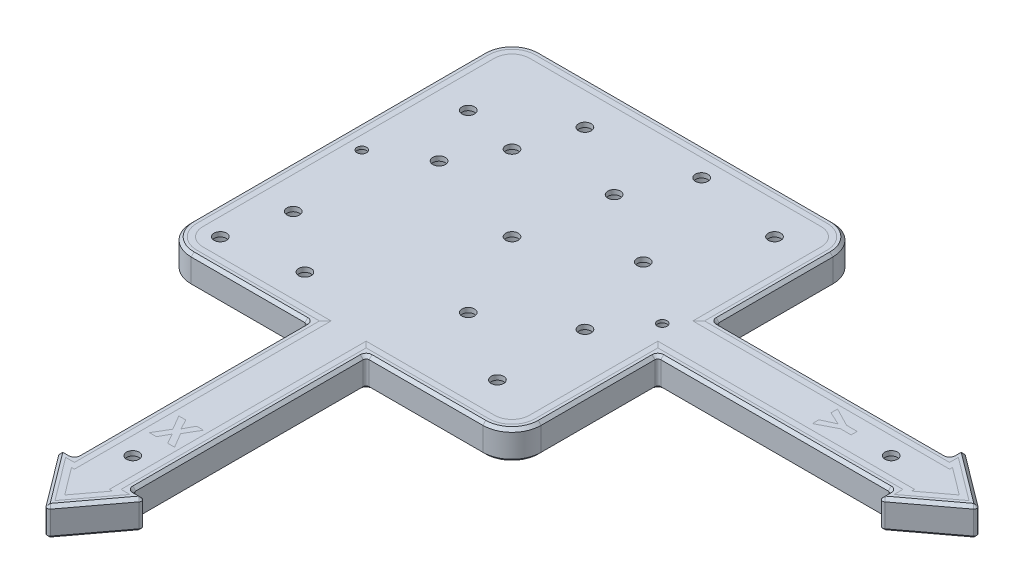
SolidWorks part; units mm, degrees
note: The reader was unsure of these and kept them because the rebuilt part matched: shared geometry of "Sketch7<3>", "Sketch7<4>", "Sketch7<5>", "Sketch7<6>", "Sketch7<7>", "Sketch8<2>", "Sketch9<2>".
ref_plane "Front Plane" through (0, 0, 0) normal (0, 0, 1) x (1, 0, 0)
ref_plane "Top Plane" through (0, 0, 0) normal (0, 1, 0) x (1, 0, 0)
ref_plane "Right Plane" through (0, 0, 0) normal (1, 0, 0) x (0, 0, -1)
sketch "Sketch1" plane through (0, 0, 0) normal (0, 1, 0) x (1, 0, 0)
  line L0 (-10, -60) -> (-10, -140)
  line L1 (-60, -60) -> (-10, -60)
  line L2 (-60, -60) -> (-60, 60)
  line L3 (-60, 60) -> (60, 60)
  line L4 (60, -60) -> (60, -10)
  line L5 (-60, -60) -> (60, 60) construction
  line L6 (-60, 60) -> (60, -60) construction
  line L7 (-10, -140) -> (10, -140)
  line L8 (10, -140) -> (10, -60)
  line L9 (60, -10) -> (140, -10)
  line L10 (140, -10) -> (140, 10)
  line L11 (140, 10) -> (60, 10)
  line L12 (0, 0) -> (140, 0) construction
  line L13 (0, 0) -> (0, -140) construction
  line L14 (10, -60) -> (60, -60)
  line L15 (60, 10) -> (60, 60)
  point P0 (0, 0)
  point P12 (140, 0)
  point P16 (0, -140)
  dimension "D1" = 120
  dimension "D2" = 20
  dimension "D3" = 80
  dimension "D4" = 120
extrude "Boss-Extrude1" add sketch "Sketch1" along normal blind 10
sketch "Sketch2" plane through (0, 10, 0) normal (0, 1, 0) x (1, 0, 0)
  line L0 (0, 0) -> (140, 0) construction
  line L1 (140, -10) -> (140, 10) construction
  line L2 (0, 0) -> (0, -140) construction
  line L3 (-10, -140) -> (10, -140) construction
  line L4 (-60, 60) -> (-60, -60) construction
  circle A0 centre (0, 0) radius 2.15
  circle A1 centre (130, 0) radius 2.15
  circle A2 centre (0, -130) radius 2.15
  circle A3 centre (40, -45) radius 2.15
  circle A4 centre (-45, -30) radius 2.15
  circle A5 centre (-26, 26) radius 2.15
  circle A6 centre (45, 45) radius 2.15
  circle A7 centre (15, 50) radius 2.15
  circle A8 centre (40, -15) radius 2.15
  circle A9 centre (-25, -46) radius 2.15
  circle A10 centre (-45, 30) radius 2.15
  circle A11 centre (-20, 45) radius 2.15
  circle A12 centre (15, -30) radius 2.15
  circle A13 centre (30, 15) radius 2.15
  circle A15 centre (-35, 10) radius 2.15
  circle A16 centre (5, 30) radius 2.15
  circle A17 centre (-50, -50) radius 2.15
  dimension "D1" = 4.3
  dimension "D12" = 50
  dimension "D21" = 40
  dimension "D22" = 35
  dimension "D23" = 15
  dimension "D24" = 30
  dimension "D25" = 15
  dimension "D26" = 30
  dimension "D27" = 10
  dimension "D28" = 50
  dimension "D29" = 50
  dimension "D30" = 30
  dimension "D31" = 5
  dimension "D2" = 130
  dimension "D3" = 130
  dimension "D4" = 40
  dimension "D5" = 45
  dimension "D6" = 45
  dimension "D7" = 30
  dimension "D8" = 26
  dimension "D9" = 26
  dimension "D10" = 45
  dimension "D11" = 45
  dimension "D13" = 15
  dimension "D14" = 30
  dimension "D15" = 45
  dimension "D16" = 46
  dimension "D17" = 25
  dimension "D18" = 40
  dimension "D19" = 15
  dimension "D20" = 45
extrude "Cut-Extrude1" cut sketch "Sketch2" against normal through all
sketch "Sketch3" plane through (0, 10, 0) normal (0, 1, 0) x (1, 0, 0)
  line L0 (-51.5, 0) -> (51.5, 0) construction
  circle A0 centre (51.5, 0) radius 1.65
  circle A1 centre (-51.5, 0) radius 1.65
  point P5 (0, 0)
  point P9 (0, 0)
  dimension "D2" = 3.3
  dimension "D1" = 103
extrude "Cut-Extrude2" cut sketch "Sketch3" against normal through all
sketch "Sketch4" plane through (0, 0, 0) normal (0, -1, 0) x (1, 0, 0)
  circle A0 centre (-45, 30) radius 5
  circle A1 centre (40, 45) radius 5
  circle A2 centre (0, 130) radius 5
  circle A3 centre (130, 0) radius 5
  circle A4 centre (0, 0) radius 5
  circle A5 centre (-26, -26) radius 5
  circle A6 centre (45, -45) radius 5
  circle A7 centre (40, 15) radius 5
  circle A8 centre (-25, 46) radius 5
  circle A9 centre (-45, -30) radius 5
  circle A10 centre (15, -50) radius 5
  circle A11 centre (15, 30) radius 5
  circle A12 centre (30, -15) radius 5
  circle A13 centre (-20, -45) radius 5
  circle A14 centre (-35, -10) radius 5
  circle A15 centre (5, -30) radius 5
  circle A16 centre (-50, 50) radius 5
  dimension "D1" = 10
extrude "Cut-Extrude3" cut sketch "Sketch4" against normal offset from surface (8.4 mm away) 1.6 up to face at (51.5, 10, 1.65)
sketch "Sketch5" plane through (0, 0, 0) normal (0, -1, 0) x (1, 0, 0)
  circle A0 centre (-51.5, 0) radius 3
  circle A1 centre (51.5, 0) radius 3
  dimension "D1" = 6
extrude "Cut-Extrude4" cut sketch "Sketch5" against normal offset from surface (9 mm away) 1 up to face at (51.5, 10, 1.65)
fillet "Fillet1" radius 10 4 edges at (-60, 5, -60) (60, 5, -60) (-60, 5, 60) (60, 5, 60)
sketch "Sketch6" plane through (0, 10, 0) normal (0, 1, 0) x (1, 0, 0)
  line L0 (0, -140) -> (0, -160) construction
  line L1 (-10, -140) -> (10, -140) construction
  line L2 (140, 0) -> (160, 0) construction
  line L3 (140, -10) -> (140, 10) construction
  line L4 (0, -140) -> (15, -140)
  line L5 (15, -140) -> (0, -160)
  line L6 (0, -160) -> (-15, -140)
  line L7 (-15, -140) -> (0, -140)
  line L8 (140, 0) -> (140, -15)
  line L9 (140, -15) -> (160, 0)
  line L10 (160, 0) -> (140, 15)
  line L11 (140, 15) -> (140, 0)
  dimension "D1" = 15
  dimension "D2" = 20
extrude "Boss-Extrude2" add sketch "Sketch6" against normal up to surface (10 mm away) up to face at (-51.5, 0, -3)
sketch "Sketch7" plane through (0, 10, 0) normal (0, 1, 0) x (1, 0, 0)
  line L36 (50, 58) -> (-50, 58)
  line L37 (-58, 50) -> (-58, -50)
  line L38 (-50, -58) -> (-8, -58)
  line L39 (-8, -58) -> (-8, -142)
  line L40 (-8, -142) -> (-11, -142)
  line L41 (-11, -142) -> (0, -156.6667)
  line L42 (0, -156.6667) -> (11, -142)
  line L43 (11, -142) -> (8, -142)
  line L44 (8, -142) -> (8, -58)
  line L45 (8, -58) -> (50, -58)
  line L46 (58, -50) -> (58, -8)
  line L47 (58, -8) -> (142, -8)
  line L48 (142, -8) -> (142, -11)
  line L49 (142, -11) -> (156.6667, 0)
  line L50 (156.6667, 0) -> (142, 11)
  line L51 (142, 11) -> (142, 8)
  line L52 (142, 8) -> (58, 8)
  line L53 (58, 8) -> (58, 50)
  line L54 (50, 58) -> (-50, 58)
  line L55 (-58, 50) -> (-58, -50)
  line L56 (-50, -58) -> (-8, -58)
  line L57 (-8, -58) -> (-8, -142)
  line L58 (-8, -142) -> (-11, -142)
  line L59 (-11, -142) -> (0, -156.6667)
  line L60 (0, -156.6667) -> (11, -142)
  line L61 (11, -142) -> (8, -142)
  line L62 (8, -142) -> (8, -58)
  line L63 (8, -58) -> (50, -58)
  line L64 (58, -50) -> (58, -8)
  line L65 (58, -8) -> (142, -8)
  line L66 (142, -8) -> (142, -11)
  line L67 (142, -11) -> (156.6667, 0)
  line L68 (156.6667, 0) -> (142, 11)
  line L69 (142, 11) -> (142, 8)
  line L70 (142, 8) -> (58, 8)
  line L71 (58, 8) -> (58, 50)
  line L72 (-6, -56) -> (-8, -58)
  line L73 (8, -58) -> (6, -56)
  line L74 (56, -6) -> (58, -8)
  line L75 (58, 8) -> (56, 6)
  line L90 (50, 56) -> (-50, 56)
  line L91 (-56, 50) -> (-56, -50)
  line L92 (-50, -56) -> (-6, -56)
  line L93 (-6, -56) -> (-6, -144)
  line L94 (-6, -144) -> (-7, -144)
  line L95 (-7, -144) -> (0, -153.3333)
  line L96 (0, -153.3333) -> (7, -144)
  line L97 (7, -144) -> (6, -144)
  line L98 (6, -144) -> (6, -56)
  line L99 (6, -56) -> (50, -56)
  line L100 (56, -50) -> (56, -6)
  line L101 (56, -6) -> (144, -6)
  line L102 (144, -6) -> (144, -7)
  line L103 (144, -7) -> (153.3333, 0)
  line L104 (153.3333, 0) -> (144, 7)
  line L105 (144, 7) -> (144, 6)
  line L106 (144, 6) -> (56, 6)
  line L107 (56, 6) -> (56, 50)
  line L108 (50, 56) -> (-50, 56)
  line L109 (-56, 50) -> (-56, -50)
  line L110 (-50, -56) -> (-6, -56)
  line L111 (-6, -56) -> (-6, -144)
  line L112 (-6, -144) -> (-7, -144)
  line L113 (-7, -144) -> (0, -153.3333)
  line L114 (0, -153.3333) -> (7, -144)
  line L115 (7, -144) -> (6, -144)
  line L116 (6, -144) -> (6, -56)
  line L117 (6, -56) -> (50, -56)
  line L118 (56, -50) -> (56, -6)
  line L119 (56, -6) -> (144, -6)
  line L120 (144, -6) -> (144, -7)
  line L121 (144, -7) -> (153.3333, 0)
  line L122 (153.3333, 0) -> (144, 7)
  line L123 (144, 7) -> (144, 6)
  line L124 (144, 6) -> (56, 6)
  line L125 (56, 6) -> (56, 50)
  arc A8 (-50, 58) -> (-58, 50) centre (-50, 50) ccw
  arc A9 (-58, -50) -> (-50, -58) centre (-50, -50) ccw
  arc A10 (50, -58) -> (58, -50) centre (50, -50) ccw
  arc A11 (58, 50) -> (50, 58) centre (50, 50) ccw
  arc A12 (-50, 58) -> (-58, 50) centre (-50, 50) ccw
  arc A13 (-58, -50) -> (-50, -58) centre (-50, -50) ccw
  arc A14 (50, -58) -> (58, -50) centre (50, -50) ccw
  arc A15 (58, 50) -> (50, 58) centre (50, 50) ccw
  arc A20 (-50, 56) -> (-56, 50) centre (-50, 50) ccw
  arc A21 (-56, -50) -> (-50, -56) centre (-50, -50) ccw
  arc A22 (50, -56) -> (56, -50) centre (50, -50) ccw
  arc A23 (56, 50) -> (50, 56) centre (50, 50) ccw
  arc A24 (-50, 56) -> (-56, 50) centre (-50, 50) ccw
  arc A25 (-56, -50) -> (-50, -56) centre (-50, -50) ccw
  arc A26 (50, -56) -> (56, -50) centre (50, -50) ccw
  arc A27 (56, 50) -> (50, 56) centre (50, 50) ccw
  dimension "D1" = 2
  dimension "D2" = 4
extrude "Cut-Extrude5" cut sketch "Sketch7" against normal blind 1 contours L116 L115 L114 L113 L112 L111 L72 L57 L58 L59 L60 L61 L62 L73
extrude "Boss-Extrude3" add sketch "Sketch7<3>" against normal up to surface (1 mm away) separate body contours L116 L115 L114 L113 L112 L111 L72 L57 L58 L59 L60 L61 L62 L73 up to face at (0, 9, 120.1429)
sketch "Sketch7<3>" plane through (0, 10, 0) normal (0, 1, 0) x (1, 0, 0) same geometry as "Sketch7"
extrude "Cut-Extrude6" cut sketch "Sketch7<4>" against normal blind 1 contours L124 L123 L122 L121 L120 L119 L74 L65 L66 L67 L68 L69 L70 L75
sketch "Sketch7<4>" plane through (0, 10, 0) normal (0, 1, 0) x (1, 0, 0) same geometry as "Sketch7"
extrude "Boss-Extrude4" add sketch "Sketch7<5>" against normal up to surface (1 mm away) separate body contours L124 L123 L122 L121 L120 L119 L74 L65 L66 L67 L68 L69 L70 L75 up to face at (120.1429, 9, 0)
sketch "Sketch7<5>" plane through (0, 10, 0) normal (0, 1, 0) x (1, 0, 0) same geometry as "Sketch7"
extrude "Cut-Extrude7" cut sketch "Sketch7<6>" against normal blind 1 contours A27 L125 L75 L71 A15 L54 A12 L55 A13 L56 L72 L110 A25 L109 A24 L108 | A26 L117 L73 L63 A14 L64 L74 L118
sketch "Sketch7<6>" plane through (0, 10, 0) normal (0, 1, 0) x (1, 0, 0) same geometry as "Sketch7"
extrude "Boss-Extrude5" add sketch "Sketch7<7>" against normal up to surface (1 mm away) separate body contours A27 L125 L75 L71 A15 L54 A12 L55 A13 L56 L72 L110 A25 L109 A24 L108 | A26 L117 L73 L63 A14 L64 L74 L118 up to face at (38.2424, 9, 38.2424)
sketch "Sketch7<7>" plane through (0, 10, 0) normal (0, 1, 0) x (1, 0, 0) same geometry as "Sketch7"
fillet "Fillet2" radius 1 14 edges at (60, 5, -10) (-10, 5, 60) (10, 5, 60) (60, 5, 10) (140, 5, 15) (140, 5, 10) (140, 5, -15) (140, 5, -10) (160, 5, 0) (-10, 5, 140) (-15, 5, 140) (0, 5, 160) (10, 5, 140) (15, 5, 140)
chamfer "Chamfer1" distance 1 angle 45 72 edges at (10, 0, 100) (10, 10, 100) (10.2929, 10, 60.2929) (10.2929, 0, 60.2929) (10.2929, 10, 139.7071) (10.2929, 0, 139.7071) (30.5, 10, 60) (30.5, 0, 60) (12, 0, 140) (57.0711, 10, 57.0711) (57.0711, 0, 57.0711) (13.8944, 0, 140.5528) (13.8944, 10, 140.5528) (60, 0, 30.5) (60, 10, 30.5) (7.3, 0, 150.2667) (60.2929, 10, 10.2929) (60.2929, 0, 10.2929) (0, 0, 159.3333) (0, 10, 159.3333) (100, 10, 10) (100, 0, 10) (-7.3, 0, 150.2667) (139.7071, 10, 10.2929) (139.7071, 0, 10.2929) (-13.8944, 0, 140.5528) (-13.8944, 10, 140.5528) (140, 0, 12) (-12, 0, 140) (140.5528, 0, 13.8944) (140.5528, 10, 13.8944) (-10.2929, 10, 139.7071) (-10.2929, 0, 139.7071) (150.2667, 0, 7.3) (-10, 10, 100) (-10, 0, 100) (159.3333, 0, 0) (159.3333, 10, 0) (-10.2929, 10, 60.2929) (-10.2929, 0, 60.2929) (150.2667, 0, -7.3) (-30.5, 0, 60) (-30.5, 10, 60) (140.5528, 0, -13.8944) (140.5528, 10, -13.8944) (-57.0711, 10, 57.0711) (-57.0711, 0, 57.0711) (140, 0, -12) (-60, 10, 0) (-60, 0, 0) (139.7071, 10, -10.2929) (139.7071, 0, -10.2929) (-57.0711, 10, -57.0711) (-57.0711, 0, -57.0711) (100, 0, -10) (100, 10, -10) (0, 0, -60) (0, 10, -60) (60.2929, 10, -10.2929) (60.2929, 0, -10.2929) (57.0711, 10, -57.0711) (57.0711, 0, -57.0711) (60, 10, -30.5) (60, 0, -30.5) (140, 10, -12) (-12, 10, 140) (150.2667, 10, -7.3) (-7.3, 10, 150.2667) (150.2667, 10, 7.3) (7.3, 10, 150.2667) (140, 10, 12) (12, 10, 140)
sketch "Sketch8" plane through (0, 10, 0) normal (0, 1, 0) x (1, 0, 0)
  line L0 (-4.1302, -120.3099) -> (3.9673, -120.3099) construction
  text T0 "X" font "Roboto" height 10
extrude "Cut-Extrude8" cut sketch "Sketch8" against normal blind 1
extrude "Boss-Extrude6" add sketch "Sketch8<2>" against normal up to surface (1 mm away) separate body up to face at (0.3282, 9, 115.2986)
sketch "Sketch8<2>" plane through (0, 10, 0) normal (0, 1, 0) x (1, 0, 0) same geometry as "Sketch8"
sketch "Sketch9" plane through (0, 10, 0) normal (0, 1, 0) x (1, 0, 0)
  line L0 (116.9469, -4) -> (116.9469, 3.8639) construction
  line L1 (56, -6) -> (144, -6) construction
  text T0 "Y" font "Roboto" height 10
  dimension "D1" = 2
extrude "Cut-Extrude9" cut sketch "Sketch9" against normal blind 1
extrude "Boss-Extrude7" add sketch "Sketch9<2>" against normal up to surface (1 mm away) separate body up to face at (111.0861, 9, -0.3322)
sketch "Sketch9<2>" plane through (0, 10, 0) normal (0, 1, 0) x (1, 0, 0) same geometry as "Sketch9"
